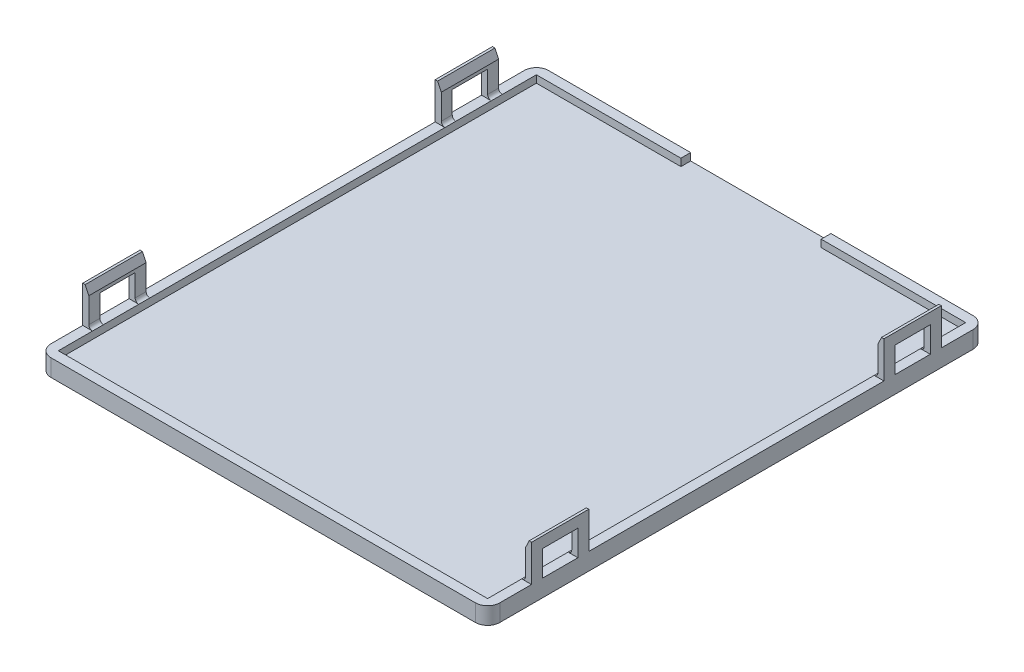
SolidWorks part; units mm, degrees
ref_plane "Ebene vorne" through (0, 0, 0) normal (0, 0, 1) x (1, 0, 0)
ref_plane "Ebene oben" through (0, 0, 0) normal (0, 1, 0) x (1, 0, 0)
ref_plane "Ebene rechts" through (0, 0, 0) normal (1, 0, 0) x (0, 0, -1)
ref_plane "Ebene1" through (0, -0.2, 0) normal (0, 1, 0) x (1, 0, 0)
sketch "Skizze1" plane through (0, -0.2, 0) normal (0, 1, 0) x (1, 0, 0)
  line L1 (-1.8, -1.8) -> (71.8, -1.8)
  line L2 (-1.8, -1.8) -> (-1.8, 79.8)
  line L3 (-1.8, 79.8) -> (71.8, 79.8)
  line L4 (71.8, -1.8) -> (71.8, 79.8)
  dimension "D1" = 1.8
  dimension "D2" = 1.8
  dimension "D3" = 79.8
  dimension "D4" = 71.8
extrude "Aufsatz-Linear austragen1" add sketch "Skizze1" against normal blind 1.6
sketch "Skizze2" plane through (0, -0.2, 0) normal (0, 1, 0) x (1, 0, 0)
  line L2 (-0.2, 78.2) -> (-0.2, -0.2)
  line L3 (-0.2, -0.2) -> (70.2, -0.2)
  line L6 (-1.8, 79.8) -> (-1.8, -1.8)
  line L7 (-1.8, -1.8) -> (71.8, -1.8)
  line L14 (71.8, 79.8) -> (71.8, -1.8)
  line L15 (70.2, 78.2) -> (70.2, -0.2)
  line L22 (70.2, 78.2) -> (-0.2, 78.2)
  line L23 (-1.8, 79.8) -> (71.8, 79.8)
  dimension "D1" = 1.6
  dimension "D2" = 1.6
  dimension "D3" = 1.6
  dimension "D4" = 1.6
  dimension "D5" = 1.8
  dimension "D6" = 1.8
  dimension "D7" = 81.6
  dimension "D8" = 73.6
extrude "Aufsatz-Linear austragen2" add sketch "Skizze2" along normal blind 1.2
ref_plane "Ebene2" through (0, 0, -78.2) normal (0, 0, 1) x (1, 0, 0)
sketch "Skizze3" plane through (0, 0, -78.2) normal (0, 0, 1) x (1, 0, 0)
  line L0 (40.48, 0) -> (-40.48, 0) construction
  line L1 (46.5, -0.2) -> (23.5, -0.2)
  line L2 (46.5, -0.2) -> (46.5, 3.8)
  line L3 (46.5, 3.8) -> (23.5, 3.8)
  line L4 (23.5, -0.2) -> (23.5, 3.8)
  line L5 (0, -4.95) -> (0, 4.95) construction
  dimension "D1" = 4
  dimension "D2" = 0.2
  dimension "D3" = 23.5
  dimension "D4" = 23
extrude "Schnitt-Linear austragen1" cut sketch "Skizze3" against normal blind 1.6
ref_plane "true_left" through (-1.8, 0, 0) normal (1, 0, 0) x (0, 0, -1)
surface "Oberfläche-Offset1" parameters "D1"=0
ref_plane "Ebene4" through (0, 0, -39) normal (0, 0, 1) x (1, 0, 0)
sketch "Skizze4" plane through (-1.8, 0, 0) normal (1, 0, 0) x (0, 0, -1)
  line L0 (63.2, 0) -> (63.2, 7)
  line L1 (72.6, 0) -> (70.8, 0)
  line L4 (70.8, 0) -> (70.8, 5.2)
  line L7 (70.8, 5.2) -> (65, 5.2)
  line L11 (63.2, 0) -> (65, 0)
  line L12 (65, 5.2) -> (65, 0)
  line L13 (63.2, 7) -> (72.6, 7)
  line L14 (72.6, 7) -> (72.6, 0)
  line L15 (40.48, 0) -> (-40.48, 0) construction
  line L17 (72.8, 7.2) -> (72.8, 1.8) construction
  line L18 (63, 1.8) -> (63, 7.2) construction
  line L19 (65.2, 5) -> (65.2, 1.8) construction
  line L20 (70.6, 1.8) -> (70.6, 5) construction
  line L21 (70.6, 5) -> (65.2, 5) construction
  line L22 (39, 4.95) -> (39, -4.95) construction
  line L23 (14.8, 7) -> (5.4, 7)
  line L24 (14.8, 0) -> (14.8, 7)
  line L25 (14.8, 0) -> (13, 0)
  line L26 (13, 5.2) -> (13, 0)
  line L27 (7.2, 5.2) -> (13, 5.2)
  line L28 (7.2, 0) -> (7.2, 5.2)
  line L29 (5.4, 0) -> (7.2, 0)
  line L30 (5.4, 7) -> (5.4, 0)
  dimension "D1" = 1.8
  dimension "D2" = 0.2
  dimension "D3" = 0.2
  dimension "D4" = 0.2
  dimension "D5" = 0.2
  dimension "D6" = 0.2
extrude "Aufsatz-Linear austragen3" add sketch "Skizze4" along normal blind 1
ref_plane "Ebene5" through (35, 0, 0) normal (1, 0, 0) x (0, 0, -1)
mirror "Spiegeln1" about plane through (35, 0, 0) normal (1, 0, 0) of "Aufsatz-Linear austragen3"
fillet "Verrundung1" radius 0.6 8 edges at (70.8, 1, -6.3) (70.8, 1, -13.9) (70.8, 1, -64.1) (70.8, 1, -71.7) (-0.8, 1, -64.1) (-0.8, 1, -71.7) (-0.8, 1, -13.9) (-0.8, 1, -6.3)
chamfer "Fase1" distance 0.6 angle 65 4 edges at (70.8, 7, -67.9) (70.8, 7, -10.1) (-0.8, 7, -10.1) (-0.8, 7, -67.9)
fillet "Verrundung2" radius 2 4 edges at (71.8, -0.4, -79.8) (71.8, -0.4, 1.8) (-1.8, -0.4, 1.8) (-1.8, -0.4, -79.8)
